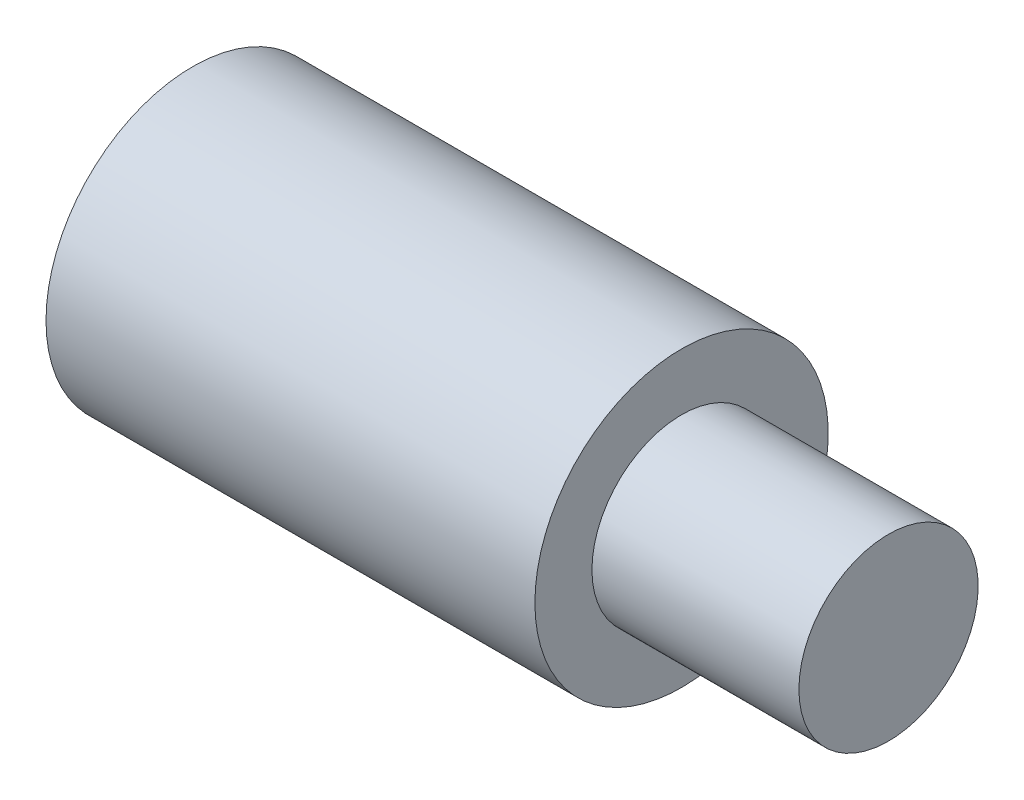
SolidWorks part; units mm, degrees
ref_plane "Front Plane" through (0, 0, 0) normal (0, 0, 1) x (1, 0, 0)
ref_plane "Top Plane" through (0, 0, 0) normal (0, 1, 0) x (1, 0, 0)
ref_plane "Right Plane" through (0, 0, 0) normal (1, 0, 0) x (0, 0, -1)
sketch "NPT_Ext_30 Sketch" plane through (0, 0, 0) normal (0, 0, 1) x (1, 0, 0)
  line L0 (-1000, 0) -> (1000, 0) construction
  line L1 (12.7, 0) -> (12.7, 5.5)
  line L2 (12.7, 5.5) -> (0, 5.5)
  line L3 (0, 5.5) -> (0, 9)
  line L4 (0, 9) -> (-30, 9)
  line L5 (-30, 9) -> (-30, 0)
  line L6 (-30, 0) -> (12.7, 0)
revolve "NPT_Ext_30" add sketch "NPT_Ext_30 Sketch" angle 360 about L0
ref_axis "Engine Axis" through (14.835, 0, 0) along (-1, 0, 0)
sketch "Socket 1 Sketch" plane through (0, 0, 0) normal (0, 0, 1) x (1, 0, 0)
  line L0 (-1000, 0) -> (1000, 0) construction
  line L1 (-31, 0) -> (-31, 5.5)
  line L2 (-31, 5.5) -> (-16, 5.5)
  line L3 (-16, 5.5) -> (-16, 0)
  line L4 (-16, 0) -> (-31, 0)
revolve "Socket 1" cut sketch "Socket 1 Sketch" angle 360 about L0
